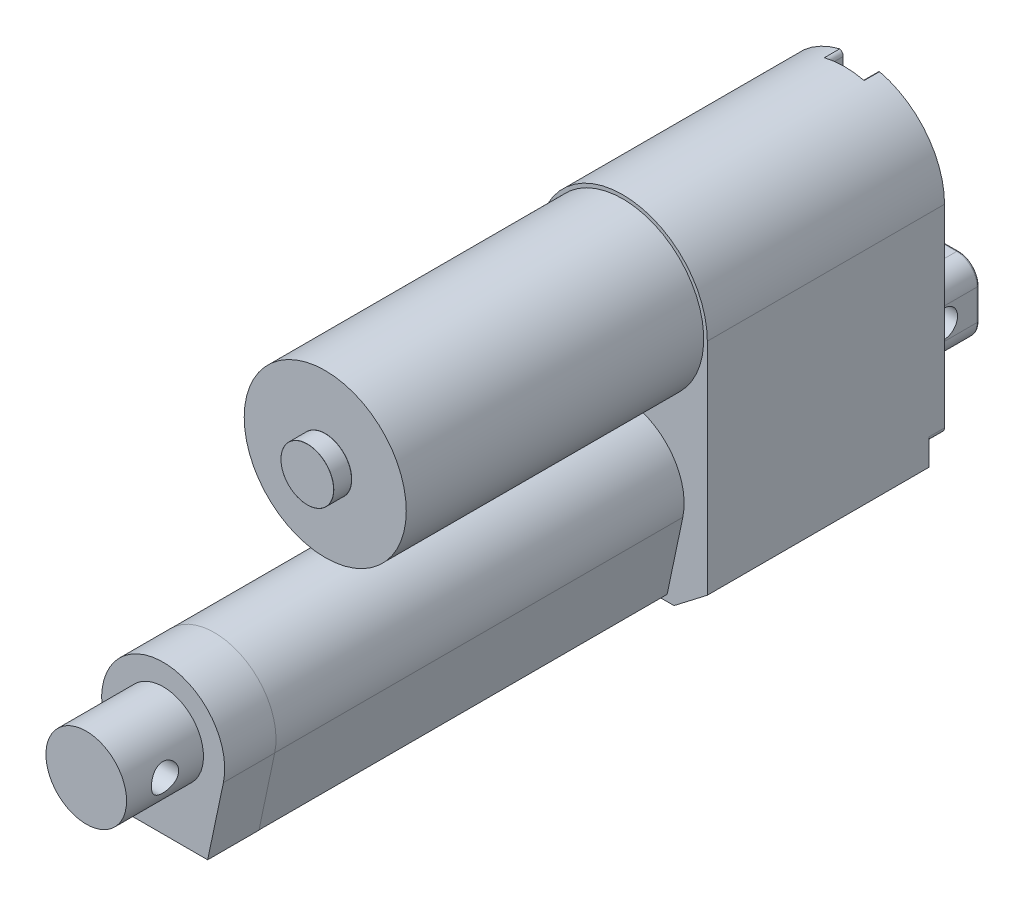
SolidWorks part; units mm, degrees
ref_plane "Front Plane" through (0, 0, 0) normal (0, 0, 1) x (1, 0, 0)
ref_plane "Top Plane" through (0, 0, 0) normal (0, 1, 0) x (1, 0, 0)
ref_plane "Right Plane" through (0, 0, 0) normal (1, 0, 0) x (0, 0, -1)
sketch "Sketch1" plane through (0, 0, 0) normal (0, 0, 1) x (1, 0, 0)
  line L0 (-12.7, 0) -> (12.7, 0)
  line L1 (-20.955, 6.35) -> (-20.955, 60.833)
  line L2 (20.955, 6.35) -> (20.955, 60.833)
  line L3 (12.7, 0) -> (20.955, 6.35)
  line L4 (-20.955, 6.35) -> (-12.7, 0)
  arc A0 (-20.955, 60.833) -> (20.955, 60.833) centre (0, 60.833) cw
  point P0 (0, 81.788)
  dimension "D7" = 81.788
  dimension "D1" = 41.91
  dimension "D2" = 8.255
  dimension "D3" = 12.7
  dimension "D4" = 8.255
  dimension "D5" = 12.7
  dimension "D6" = 6.35
extrude "Boss-Extrude1" add sketch "Sketch1" along normal blind 58.7375
sketch "Sketch2" plane through (0, 0, 58.7375) normal (0, 0, 1) x (1, 0, 0)
  circle A0 centre (0, 60.833) radius 20.066
  arc A1 (20.955, 60.833) -> (-20.955, 60.833) centre (0, 60.833) ccw construction
  dimension "D1" = 40.132
extrude "Boss-Extrude2" add sketch "Sketch2" along normal blind 73.66
sketch "Sketch3" plane through (0, 0, 58.7375) normal (0, 0, 1) x (1, 0, 0)
  line L0 (-12.7, 0) -> (12.7, 0) construction
  line L1 (-14.8881, 20.0427) -> (-10.9969, 1.5621)
  line L2 (-10.9969, 1.5621) -> (10.9969, 1.5621)
  line L3 (10.9969, 1.5621) -> (14.8881, 20.0427)
  line L5 (-10.9969, 1.5621) -> (-10.668, 0) construction
  line L6 (10.9969, 1.5621) -> (10.668, 0) construction
  arc A0 (14.8881, 20.0427) -> (-14.8881, 20.0427) centre (0, 23.1775) ccw
  point P1 (0, 1.5621)
  point P6 (15.2146, 23.1775)
  point P11 (-15.2146, 23.1775)
  point P16 (0, 38.3921)
  dimension "D1" = 23.1775
  dimension "D3" = 36.83
  dimension "D2" = 30.4292
  dimension "D4" = 21.336
extrude "EDIT_LENGTH_HERE (hover for comment)" add sketch "Sketch3" along normal blind 113.792
sketch "Sketch4" plane through (0, 0, 172.5295) normal (0, 0, 1) x (1, 0, 0)
  circle A0 centre (0, 23.1775) radius 9.9822
  arc A1 (14.8881, 20.0427) -> (-14.8881, 20.0427) centre (0, 23.1775) ccw construction
  dimension "D3" = 19.9644
extrude "Boss-Extrude4" add sketch "Sketch4" along normal blind 19.05
sketch "Sketch5" plane through (0, 0, 0) normal (0, 0, -1) x (-1, 0, 0)
  line L0 (12.7, 0) -> (-12.7, 0) construction
  line L1 (-3.81, 32.0675) -> (3.81, 32.0675)
  line L2 (-8.89, 26.9875) -> (-8.89, 19.3675)
  line L3 (-3.81, 14.2875) -> (3.81, 14.2875)
  line L4 (8.89, 26.9875) -> (8.89, 19.3675)
  line L5 (-8.89, 32.0675) -> (8.89, 14.2875) construction
  line L6 (-8.89, 14.2875) -> (8.89, 32.0675) construction
  arc A0 (-8.89, 19.3675) -> (-3.81, 14.2875) centre (-3.81, 19.3675) ccw
  arc A1 (3.81, 14.2875) -> (8.89, 19.3675) centre (3.81, 19.3675) ccw
  arc A2 (3.81, 32.0675) -> (8.89, 26.9875) centre (3.81, 26.9875) cw
  arc A3 (-3.81, 32.0675) -> (-8.89, 26.9875) centre (-3.81, 26.9875) ccw
  point P0 (0, 23.1775)
  dimension "D4" = 5.08
  dimension "D1" = 17.78
  dimension "D2" = 17.78
  dimension "D3" = 14.2875
extrude "Boss-Extrude5" add sketch "Sketch5" along normal blind 20.6502
sketch "Sketch6" plane through (8.89, 0, 0) normal (1, 0, 0) x (0, 0, -1)
  line L0 (11.9062, 14.2875) -> (11.9062, 32.0675) construction
  line L1 (0, 26.9875) -> (0, 19.3675) construction
  line L2 (20.6502, 14.2875) -> (0, 14.2875) construction
  line L3 (-191.5795, 33.1597) -> (-191.5795, 13.1953) construction
  line L4 (20.6502, 32.0675) -> (0, 32.0675) construction
  circle A0 centre (11.9062, 23.1775) radius 3.3782
  circle A1 centre (-182.0545, 23.1775) radius 3.3782
  dimension "D1" = 6.7564
  dimension "D3" = 6.7564
  dimension "D2" = 11.9062
  dimension "D4" = 9.525
extrude "Cut-Extrude3" cut sketch "Sketch6" against normal through all and the other way through all
fillet "Fillet1" radius 2.54 8 edges at (-7.4021, 15.7754, 0) (0, 14.2875, 0) (7.4021, 15.7754, 0) (8.89, 23.1775, 0) (7.4021, 30.5796, 0) (0, 32.0675, 0) (-7.4021, 30.5796, 0) (-8.89, 23.1775, 0)
fillet "Fillet2" radius 0.508 8 edges at (8.89, 23.1775, -20.6502) (7.4021, 30.5796, -20.6502) (0, 32.0675, -20.6502) (-7.4021, 30.5796, -20.6502) (-8.89, 23.1775, -20.6502) (-7.4021, 15.7754, -20.6502) (0, 14.2875, -20.6502) (7.4021, 15.7754, -20.6502)
sketch "Sketch7" plane through (0, 0, 0) normal (0, 0, -1) x (-1, 0, 0)
  line L0 (-4.1275, 77.089) -> (-4.1275, 80.0683)
  line L1 (4.1275, 77.089) -> (4.1275, 79.9786)
  line L2 (-20.955, 6.35) -> (-20.955, 60.833) construction
  line L3 (20.955, 60.833) -> (20.955, 6.35) construction
  line L4 (-13.3956, 1.8544) -> (-11.2223, 6.0477)
  line L5 (-14.605, 11.6109) -> (-19.685, 11.6109)
  line L6 (11.5416, 5.5356) -> (13.4023, 1.8413)
  line L7 (14.605, 11.6109) -> (19.685, 11.6109)
  line L8 (20.955, 6.35) -> (12.7, 0) construction
  line L9 (-12.7, 0) -> (-20.955, 6.35) construction
  line L10 (-20.955, 6.35) -> (-20.955, 12.8809)
  line L11 (12.7, 0) -> (-12.7, 0) construction
  line L12 (-12.7, 0) -> (-20.955, 6.35)
  line L13 (20.955, 12.8809) -> (20.955, 6.35)
  line L14 (20.955, 6.35) -> (12.7, 0)
  arc A0 (-4.1275, 77.089) -> (4.1275, 77.089) centre (0, 77.089) ccw
  arc A1 (20.955, 60.833) -> (-20.955, 60.833) centre (0, 60.833) ccw construction
  arc A2 (6.3689, 80.7967) -> (-6.4572, 80.7683) centre (0, 60.833) ccw
  arc A3 (-6.4572, 80.7683) -> (-4.1275, 80.0683) centre (-5.3975, 80.0683) cw
  arc A4 (4.1275, 79.9786) -> (6.3689, 80.7967) centre (5.3975, 79.9786) cw
  arc A5 (-11.2223, 6.0477) -> (-14.605, 11.6109) centre (-14.605, 7.8009) ccw
  arc A6 (14.605, 11.6109) -> (11.5416, 5.5356) centre (14.605, 7.8009) ccw
  arc A7 (13.4023, 1.8413) -> (12.268, 0) centre (12.268, 1.27) cw
  arc A8 (-13.3956, 1.8544) -> (-12.268, 0) centre (-12.268, 1.27) ccw
  arc A9 (19.685, 11.6109) -> (20.955, 12.8809) centre (19.685, 12.8809) ccw
  arc A10 (-19.685, 11.6109) -> (-20.955, 12.8809) centre (-19.685, 12.8809) cw
  point P12 (4.6513, 81.2653)
  point P39 (20.955, 11.6109)
  point P42 (-20.955, 11.6109)
  line M10 (20.955, 6.35) -> (20.955, 60.833)
  arc M11 (20.955, 60.833) -> (-20.955, 60.833) centre (0, 60.833) ccw
  line M12 (-20.955, 60.833) -> (-20.955, 6.35)
  line M13 (-20.955, 6.35) -> (-12.7, 0)
  dimension "D1" = 8.255
  dimension "D2" = 1.27
  dimension "D3" = 1.27
  dimension "D5" = 7.62
  dimension "D8" = 1.27
  dimension "D9" = 1.27
  dimension "D4" = 16.256
  dimension "D6" = 6.35
  dimension "D7" = 6.35
extrude "Cut-Extrude5" cut sketch "Sketch7" against normal blind 3.81 contours L1 A4 A3 L0 A0 M11 | L5 A10 A8 L4 A5 M12 M13 | A9 L7 A6 L6 A7 L14 M10 region at (15.8698, 7.3642, 0) region at (-15.875, 7.3683, 0) region at (-0.005, 77.7298, 0)
sketch "Sketch8" plane through (0, 0, 132.3975) normal (0, 0, 1) x (1, 0, 0)
  circle A0 centre (0, 60.833) radius 6.5405
  dimension "D1" = 13.081
extrude "Boss-Extrude6" add sketch "Sketch8" along normal blind 4.445
fillet "Fillet3" radius 0.0254 2 edges at (6.5405, 60.833, 132.3975) (6.5405, 60.833, 136.8425)
sketch "Sketch9" plane through (0, 0, 172.5295) normal (0, 0, 1) x (1, 0, 0)
  line L0 (10.9969, 1.5621) -> (14.8881, 20.0427) construction
  line L1 (-14.8881, 20.0427) -> (-10.9969, 1.5621) construction
  line L2 (-10.9969, 1.5621) -> (10.9969, 1.5621) construction
  line L3 (10.9969, 1.5621) -> (14.8881, 20.0427)
  line L4 (-14.8881, 20.0427) -> (-10.9969, 1.5621)
  line L5 (-10.9969, 1.5621) -> (10.9969, 1.5621)
  line L6 (-11.0175, 1.5367) -> (11.0175, 1.5367)
  line L7 (11.0175, 1.5367) -> (14.913, 20.0374)
  line L8 (-14.913, 20.0374) -> (-11.0175, 1.5367)
  arc A0 (14.8881, 20.0427) -> (-14.8881, 20.0427) centre (0, 23.1775) ccw construction
  arc A1 (14.8881, 20.0427) -> (-14.8881, 20.0427) centre (0, 23.1775) ccw
  arc A2 (14.913, 20.0374) -> (-14.913, 20.0374) centre (0, 23.1775) ccw
  dimension "D1" = 0.0254
extrude "Boss-Extrude7" add sketch "Sketch9" against normal blind 12.7
sketch "Sketch10" plane through (0, 0, 3.81) normal (0, 0, -1) x (-1, 0, 0)
  circle A0 centre (0, 77.089) radius 2.54
  circle A1 centre (-14.605, 7.8009) radius 2.54
  circle A2 centre (14.605, 7.8009) radius 2.54
  dimension "D1" = 5.08
extrude "Boss-Extrude8" add sketch "Sketch10" along normal blind 0.635
sketch "Sketch12" plane through (0, 0, 3.175) normal (0, 0, -1) x (-1, 0, 0)
  line L0 (0.3175, 74.3343) -> (0.3175, 75.8444)
  line L1 (-0.2921, 78.359) -> (0.2921, 78.359)
  line L2 (-0.3175, 78.3336) -> (-0.3175, 77.5335)
  line L3 (-0.2921, 75.819) -> (0.2921, 75.819)
  line L4 (0.3175, 78.3336) -> (0.3175, 77.5335)
  line L5 (-0.3175, 78.359) -> (0.3175, 75.819) construction
  line L6 (-0.3175, 75.819) -> (0.3175, 78.359) construction
  line L7 (-1.2446, 77.4065) -> (-0.4445, 77.4065)
  line L8 (-1.27, 77.3811) -> (-1.27, 76.7969)
  line L9 (-1.2446, 76.7715) -> (-0.4445, 76.7715)
  line L10 (1.27, 77.3811) -> (1.27, 76.7763)
  line L11 (-1.27, 77.4065) -> (1.27, 76.7715) construction
  line L12 (-1.27, 76.7715) -> (1.27, 77.4065) construction
  line L13 (0.3264, 74.381) -> (1.2682, 76.767)
  line L14 (-14.2875, 7.3564) -> (-14.2875, 6.5563)
  line L15 (0.4445, 77.4065) -> (1.2446, 77.4065)
  line L16 (-0.3175, 76.6445) -> (-0.3175, 75.8444)
  line L17 (-14.8971, 9.0709) -> (-14.3129, 9.0709)
  line L18 (-14.9225, 9.0455) -> (-14.9225, 8.2454)
  line L19 (-14.8971, 6.5309) -> (-14.3129, 6.5309)
  line L20 (-14.2875, 9.0455) -> (-14.2875, 8.2454)
  line L21 (-14.9225, 9.0709) -> (-14.2875, 6.5309) construction
  line L22 (-14.9225, 6.5309) -> (-14.2875, 9.0709) construction
  line L23 (-15.8496, 8.1184) -> (-15.0495, 8.1184)
  line L24 (-15.875, 8.093) -> (-15.875, 7.5088)
  line L25 (-15.8496, 7.4834) -> (-15.0495, 7.4834)
  line L26 (-13.335, 8.093) -> (-13.335, 7.5088)
  line L27 (-15.875, 8.1184) -> (-13.335, 7.4834) construction
  line L28 (-15.875, 7.4834) -> (-13.335, 8.1184) construction
  line L29 (-14.1605, 7.4834) -> (-13.3604, 7.4834)
  line L30 (-14.1605, 8.1184) -> (-13.3604, 8.1184)
  line L31 (-14.9225, 7.3564) -> (-14.9225, 6.5563)
  line L32 (14.9225, 7.3564) -> (14.9225, 6.5563)
  line L33 (14.3129, 9.0709) -> (14.8971, 9.0709)
  line L34 (14.2875, 9.0455) -> (14.2875, 8.2454)
  line L35 (14.3129, 6.5309) -> (14.8971, 6.5309)
  line L36 (14.9225, 9.0455) -> (14.9225, 8.2454)
  line L37 (14.2875, 9.0709) -> (14.9225, 6.5309) construction
  line L38 (14.2875, 6.5309) -> (14.9225, 9.0709) construction
  line L39 (13.3604, 8.1184) -> (14.1605, 8.1184)
  line L40 (13.335, 8.093) -> (13.335, 7.5088)
  line L41 (13.3604, 7.4834) -> (14.1605, 7.4834)
  line L42 (15.875, 8.093) -> (15.875, 7.5088)
  line L43 (13.335, 8.1184) -> (15.875, 7.4834) construction
  line L44 (13.335, 7.4834) -> (15.875, 8.1184) construction
  line L45 (15.0495, 7.4834) -> (15.8496, 7.4834)
  line L46 (15.0495, 8.1184) -> (15.8496, 8.1184)
  line L47 (14.2875, 7.3564) -> (14.2875, 6.5055)
  arc A0 (-0.4445, 76.7715) -> (-0.3175, 76.6445) centre (-0.4445, 76.6445) cw
  arc A1 (0.3264, 74.381) -> (0.3175, 74.3343) centre (0.4445, 74.3343) ccw
  arc A2 (0.3175, 77.5335) -> (0.4445, 77.4065) centre (0.4445, 77.5335) ccw
  arc A3 (-0.4445, 77.4065) -> (-0.3175, 77.5335) centre (-0.4445, 77.5335) ccw
  arc A4 (-1.2446, 77.4065) -> (-1.27, 77.3811) centre (-1.2446, 77.3811) ccw
  arc A5 (-1.27, 76.7969) -> (-1.2446, 76.7715) centre (-1.2446, 76.7969) ccw
  arc A6 (-0.3175, 75.8444) -> (-0.2921, 75.819) centre (-0.2921, 75.8444) ccw
  arc A7 (0.2921, 75.819) -> (0.3175, 75.8444) centre (0.2921, 75.8444) ccw
  arc A8 (1.2682, 76.767) -> (1.27, 76.7763) centre (1.2446, 76.7763) ccw
  arc A9 (1.2446, 77.4065) -> (1.27, 77.3811) centre (1.2446, 77.3811) cw
  arc A10 (0.2921, 78.359) -> (0.3175, 78.3336) centre (0.2921, 78.3336) cw
  arc A11 (-0.2921, 78.359) -> (-0.3175, 78.3336) centre (-0.2921, 78.3336) ccw
  arc A12 (-15.0495, 7.4834) -> (-14.9225, 7.3564) centre (-15.0495, 7.3564) cw
  arc A13 (-14.1605, 7.4834) -> (-14.2875, 7.3564) centre (-14.1605, 7.3564) ccw
  arc A14 (-14.2875, 8.2454) -> (-14.1605, 8.1184) centre (-14.1605, 8.2454) ccw
  arc A15 (-15.0495, 8.1184) -> (-14.9225, 8.2454) centre (-15.0495, 8.2454) ccw
  arc A16 (-15.8496, 8.1184) -> (-15.875, 8.093) centre (-15.8496, 8.093) ccw
  arc A17 (-15.875, 7.5088) -> (-15.8496, 7.4834) centre (-15.8496, 7.5088) ccw
  arc A18 (-14.9225, 6.5563) -> (-14.8971, 6.5309) centre (-14.8971, 6.5563) ccw
  arc A19 (-14.3129, 6.5309) -> (-14.2875, 6.5563) centre (-14.3129, 6.5563) ccw
  arc A20 (-13.3604, 7.4834) -> (-13.335, 7.5088) centre (-13.3604, 7.5088) ccw
  arc A21 (-13.3604, 8.1184) -> (-13.335, 8.093) centre (-13.3604, 8.093) cw
  arc A22 (-14.3129, 9.0709) -> (-14.2875, 9.0455) centre (-14.3129, 9.0455) cw
  arc A23 (-14.8971, 9.0709) -> (-14.9225, 9.0455) centre (-14.8971, 9.0455) ccw
  arc A26 (14.1605, 7.4834) -> (14.2875, 7.3564) centre (14.1605, 7.3564) cw
  arc A27 (15.0495, 7.4834) -> (14.9225, 7.3564) centre (15.0495, 7.3564) ccw
  arc A28 (14.9225, 8.2454) -> (15.0495, 8.1184) centre (15.0495, 8.2454) ccw
  arc A29 (14.1605, 8.1184) -> (14.2875, 8.2454) centre (14.1605, 8.2454) ccw
  arc A30 (13.3604, 8.1184) -> (13.335, 8.093) centre (13.3604, 8.093) ccw
  arc A31 (13.335, 7.5088) -> (13.3604, 7.4834) centre (13.3604, 7.5088) ccw
  arc A32 (14.2875, 6.5055) -> (14.3129, 6.5309) centre (14.3129, 6.5055) ccw
  arc A33 (14.8971, 6.5309) -> (14.9225, 6.5563) centre (14.8971, 6.5563) ccw
  arc A34 (15.8496, 7.4834) -> (15.875, 7.5088) centre (15.8496, 7.5088) ccw
  arc A35 (15.8496, 8.1184) -> (15.875, 8.093) centre (15.8496, 8.093) cw
  arc A36 (14.8971, 9.0709) -> (14.9225, 9.0455) centre (14.8971, 9.0455) cw
  arc A37 (14.3129, 9.0709) -> (14.2875, 9.0455) centre (14.3129, 9.0455) ccw
  point P0 (0, 77.089)
  point P6 (0, 77.089)
  point P16 (-0.3175, 76.7715)
  point P20 (0.3175, 74.3585)
  point P23 (0.3175, 77.4065)
  point P50 (-14.605, 7.8009)
  point P55 (-14.605, 7.8009)
  point P96 (14.605, 7.8009)
  point P101 (14.605, 7.8009)
  dimension "D5" = 0.127
  dimension "D6" = 0.0254
  dimension "D11" = 0.127
  dimension "D12" = 0.0254
  dimension "D17" = 0.127
  dimension "D18" = 0.0254
  dimension "D1" = 0.635
  dimension "D2" = 2.54
  dimension "D3" = 0.635
  dimension "D4" = 2.54
  dimension "D7" = 0.635
  dimension "D8" = 2.54
  dimension "D9" = 0.635
  dimension "D10" = 2.54
  dimension "D13" = 0.635
  dimension "D14" = 2.54
  dimension "D15" = 0.635
  dimension "D16" = 2.54
dome "Dome1" [suppressed] faces to dome 3 distance 1.27 parameters "D1"=1.27
extrude "Cut-Extrude7" [suppressed] cut sketch "Sketch12" along normal up to next
